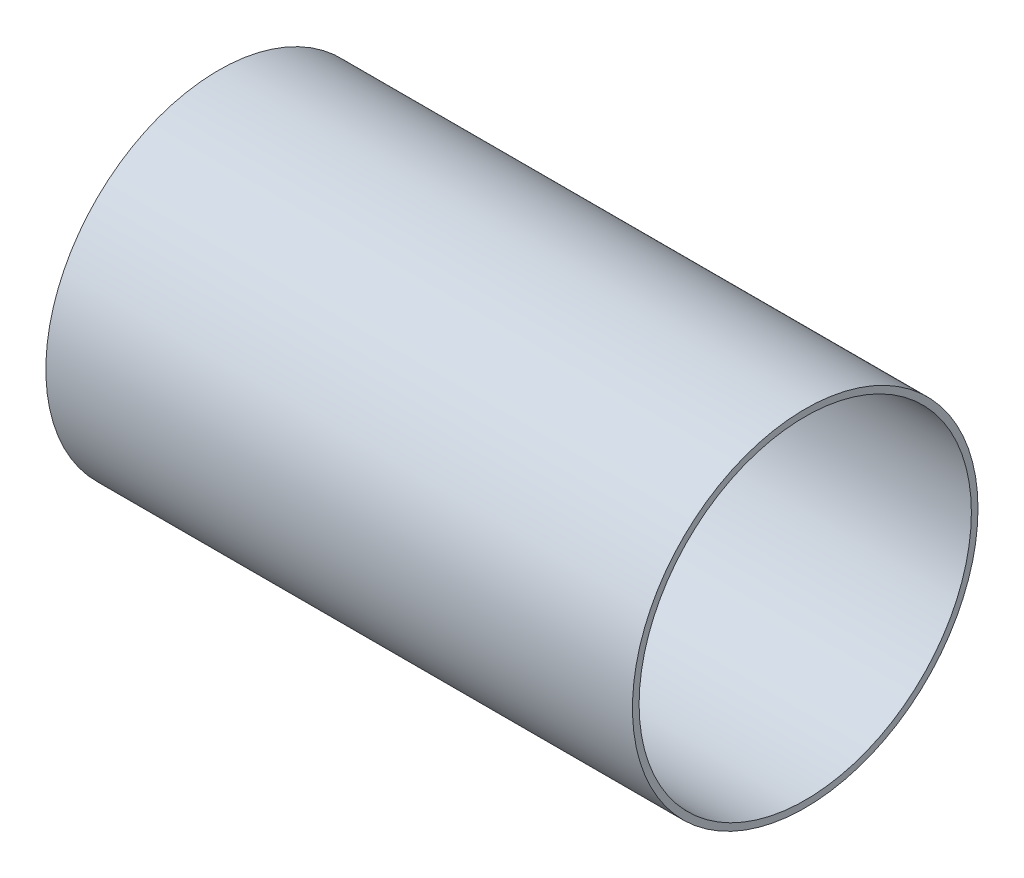
SolidWorks part; units mm, degrees
ref_plane "Front Plane" through (0, 0, 0) normal (0, 0, 1) x (1, 0, 0)
ref_plane "Top Plane" through (0, 0, 0) normal (0, 1, 0) x (1, 0, 0)
ref_plane "Right Plane" through (0, 0, 0) normal (1, 0, 0) x (0, 0, -1)
sketch "Sketch1" plane through (0, 0, 0) normal (1, 0, 0) x (0, 0, -1)
  circle A0 centre (0, 0) radius 21.0058
  circle A1 centre (0, 0) radius 21.844
  dimension "D1" = 43.688
  dimension "D2" = 0.8382
extrude "Boss-Extrude1" add sketch "Sketch1" along normal blind 74.168
